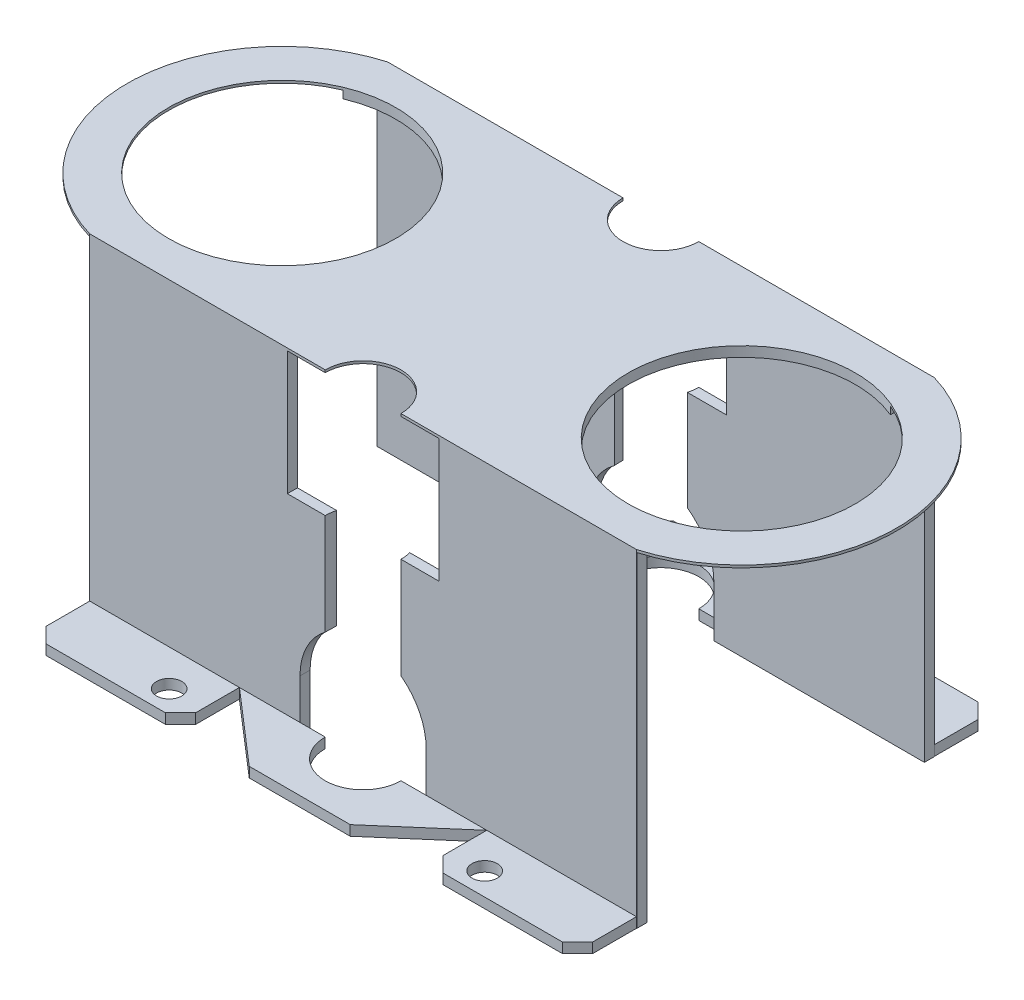
SolidWorks part; units mm, degrees
ref_plane "Front Plane" through (0, 0, 0) normal (0, 0, 1) x (1, 0, 0)
ref_plane "Top Plane" through (0, 0, 0) normal (0, 1, 0) x (1, 0, 0)
ref_plane "Right Plane" through (0, 0, 0) normal (1, 0, 0) x (0, 0, -1)
sketch "Sketch1" plane through (0, 0, 0) normal (0, 0, 1) x (1, 0, 0)
  line L0 (0, 0) -> (0, 55340.2053) construction
  line L1 (0, 0) -> (55340.2053, 0) construction
  line L2 (-542, 0) -> (-542, 645)
  line L3 (542, 0) -> (542, 645)
  line L4 (-542, 645) -> (-769.1429, 645)
  line L6 (542, 645) -> (769.1429, 645)
  line L7 (-769.1429, 645) -> (-769.1429, 650)
  line L8 (769.1429, 645) -> (769.1429, 650)
  line L9 (-769.1429, 650) -> (769.1429, 650)
  line L10 (-542, 645) -> (542, 645)
  line L11 (-150, 645) -> (-150, 400)
  line L12 (150, 645) -> (150, 400)
  line L13 (-150, 400) -> (150, 400)
  line L14 (-542, 0) -> (-125, 0)
  line L15 (542, 0) -> (125, 0)
  line L16 (-125, 0) -> (-125, 99.9278)
  line L17 (125, 0) -> (125, 99.9278)
  arc A0 (-125, 99.9278) -> (125, 99.9278) centre (0, 99.9278) cw
  point P14 (0, 650)
  point P15 (0, 645)
  point P20 (0, 400)
  point P26 (0, 0)
  dimension "D5" = 392
  dimension "D1" = 650
  dimension "D2" = 250
  dimension "D3" = 300
  dimension "D4" = 250
  dimension "D6" = 5
  dimension "D7" = 769.1429
  dimension "D8" = 99.9278
extrude "Boss-Extrude1" add sketch "Sketch1" along normal blind 590 contours L16 A0 L17 L15 L3 L10 L12 L13 L11 L2 L14 | L4 L10 L6 L8 L9 L7 region at (0, 316.0246, 0) region at (0, 647.5, 0)
sketch "Sketch2" plane through (0, 650, 0) normal (0, 1, 0) x (1, 0, 0)
  line L0 (0, 0) -> (0, 50000) construction
  line L1 (-769.1429, 0) -> (769.1429, 0) construction
  line L2 (-769.1429, -590) -> (769.1429, -590) construction
  line L3 (-541.5, 0) -> (-541.5, 86.663)
  line L4 (-511.5, 116.663) -> (-274.9962, 116.663)
  line L5 (-244.9962, 86.663) -> (-244.9962, 0)
  line L6 (-244.9962, 0) -> (-100, 125.5124)
  line L7 (-100, 125.5124) -> (100, 125.5124)
  line L8 (100, 125.5124) -> (244.9962, 0)
  line L9 (244.9962, 0) -> (244.9962, 86.663)
  line L10 (274.9962, 116.663) -> (511.5, 116.663)
  line L11 (541.5, 86.663) -> (541.5, 0)
  line L12 (0, -295) -> (50000, -295) construction
  line L13 (244.9962, -590) -> (244.9962, -676.663)
  line L14 (541.5, -676.663) -> (541.5, -590)
  line L15 (274.9962, -706.663) -> (511.5, -706.663)
  line L16 (100, -715.5124) -> (244.9962, -590)
  line L17 (-100, -715.5124) -> (100, -715.5124)
  line L18 (-244.9962, -590) -> (-100, -715.5124)
  line L19 (-244.9962, -676.663) -> (-244.9962, -590)
  line L20 (-541.5, -590) -> (-541.5, -676.663)
  line L21 (-511.5, -706.663) -> (-274.9962, -706.663)
  line L22 (-541.5, 0) -> (541.5, 0)
  line L23 (-541.5, -590) -> (541.5, -590)
  line L24 (-541.5, 86.663) -> (-511.5, 116.663)
  line L25 (-274.9962, 116.663) -> (-244.9962, 86.663)
  line L26 (244.9962, 86.663) -> (274.9962, 116.663)
  line L27 (511.5, 116.663) -> (541.5, 86.663)
  line L28 (511.5, -706.663) -> (541.5, -676.663)
  line L29 (244.9962, -676.663) -> (274.9962, -706.663)
  line L30 (-274.9962, -706.663) -> (-244.9962, -676.663)
  line L31 (-541.5, -676.663) -> (-511.5, -706.663)
  line L32 (-769.1429, -590) -> (-769.1429, 0) construction
  circle A0 centre (-455.2517, -295) radius 242.5
  circle A1 centre (-455.2517, -295) radius 225
  circle A2 centre (0, -590) radius 75
  circle A3 centre (0, 0) radius 75
  circle A4 centre (455.2517, -295) radius 242.5
  circle A5 centre (455.2517, -295) radius 225
  circle A6 centre (-312.5, -661.663) radius 25
  circle A7 centre (-312.5, 71.663) radius 25
  circle A8 centre (312.5, 71.663) radius 25
  circle A9 centre (312.5, -661.663) radius 25
  arc A10 (-541.5, 0) -> (-541.5, -590) centre (-455.2517, -295) ccw
  arc A11 (541.5, 0) -> (541.5, -590) centre (455.2517, -295) cw
  point P4 (0, 0)
  point P16 (-541.5, 116.663)
  point P18 (-244.9962, 116.663)
  point P23 (244.9962, 116.663)
  point P24 (541.5, 116.663)
  point P28 (244.9962, -706.663)
  point P29 (541.5, -706.663)
  point P34 (-244.9962, -706.663)
  point P36 (-541.5, -706.663)
  point P49 (762.6013, -295)
  point P50 (-762.6013, -295)
  point P51 (455.2614, -295)
  point P53 (0, 0)
  point P54 (0, 0)
  point P56 (-387.911, 131.386)
  line M28 (769.1429, 0) -> (-769.1429, 0)
  line M29 (-769.1429, 0) -> (-769.1429, -590)
  line M30 (-769.1429, -590) -> (769.1429, -590)
  line M31 (769.1429, -590) -> (769.1429, 0)
  dimension "D2" = 450
  dimension "D3" = 485
  dimension "D4" = 150
  dimension "D5" = 150
  dimension "D14" = 50
  dimension "D1" = 295
  dimension "D6" = 200
  dimension "D7" = 625
  dimension "D8" = 1083
  dimension "D9" = 1525.2026
  dimension "D10" = 45
  dimension "D11" = 625
  dimension "D12" = 45
  dimension "D13" = 45
extrude "Boss-Extrude2" add sketch "Sketch2" against normal blind 650 contours L25 L4 L24 L3 L5 A7 M28 | A3 L8 L7 L6 M28 | L27 L10 L26 L9 L11 A8 M28 | L13 L29 L15 L28 L14 A9 M30 | A2 L18 L17 L16 M30 | L20 L31 L21 L30 L19 A6 M30 region at (-398.2453, 650, -56.1355) region at (-169.1876, 650, -58.9319) region at (-398.2453, 650, 646.1355) region at (-159.9981, 650, 595.0581) region at (398.2453, 650, -56.1355) region at (398.2453, 650, 646.1355)
extrude "Cut-Extrude2" cut sketch "Sketch2<4>" against normal through all contours A1 | A5 | L23 A2 | L22 A3 | A10 M28 M29 M30 | A11 M28 M30 M31 region at (-768.9252, 650, 295) region at (0, 650, 31.831) region at (0, 650, 558.169) region at (655.3214, 650, 6.3239) region at (-455.2517, 650, 295) region at (455.2517, 650, 295)
sketch "Sketch2<4>" plane through (0, 650, 0) normal (0, 1, 0) x (1, 0, 0) same geometry as "Sketch2"
sketch "Sketch3" plane through (541.5, 0, 0) normal (1, 0, 0) x (0, 0, -1)
  line L0 (-716.88, 20) -> (-590, 20)
  line L1 (-590, 0) -> (-590, 650) construction
  line L2 (-590, 20) -> (-590, 650)
  line L3 (-716.88, 20) -> (-716.88, 0)
  line L4 (-716.88, 0) -> (-570, 0)
  line L5 (-570, 0) -> (-570, 630)
  line L6 (-570, 630) -> (-20, 630)
  line L7 (-20, 630) -> (-20, 0)
  line L8 (-20, 0) -> (151.9541, 0)
  line L9 (151.9541, 0) -> (151.9541, 20)
  line L10 (151.9541, 20) -> (0, 20)
  line L11 (0, 0) -> (0, 650) construction
  line L12 (0, 20) -> (0, 650)
  line L13 (-590, 650) -> (0, 650)
  line L15 (0, 650) -> (176.905, 650)
  line L16 (0, 650) -> (0, 20)
  line L17 (0, 20) -> (176.905, 20)
  line L18 (176.905, 650) -> (176.905, 20)
  line L19 (-570, 630) -> (-20, 630)
  line L20 (-570, 630) -> (-570, -112.4041)
  line L21 (-570, -112.4041) -> (-20, -112.4041)
  line L22 (-20, 630) -> (-20, -112.4041)
  line L23 (-590, 650) -> (-864.9554, 650)
  line L24 (-590, 650) -> (-590, 20)
  line L25 (-590, 20) -> (-864.9554, 20)
  line L26 (-864.9554, 650) -> (-864.9554, 20)
  point P4 (65.977, 0)
  line M13 (86.663, 650) -> (0, 650)
  line M14 (0, 650) -> (0, 0)
  line M16 (86.663, 0) -> (86.663, 650)
  dimension "D1" = 20
  dimension "D2" = 20
  dimension "D3" = 20
  dimension "D4" = 20
  dimension "D5" = 20
extrude "Cut-Extrude4" cut sketch "Sketch3" against normal through all both and the other way through all contours L23 L26 L25 L0 L2 | L18 L15 L10 L17 M16 | L10 M16 M13 M14 | L22 L7 L6 L5 L20 L21 region at (541.5, 335, 727.4777) region at (541.5, 258.798, 295) region at (541.5, 335, -43.3315) region at (541.5, 335, -131.784)
